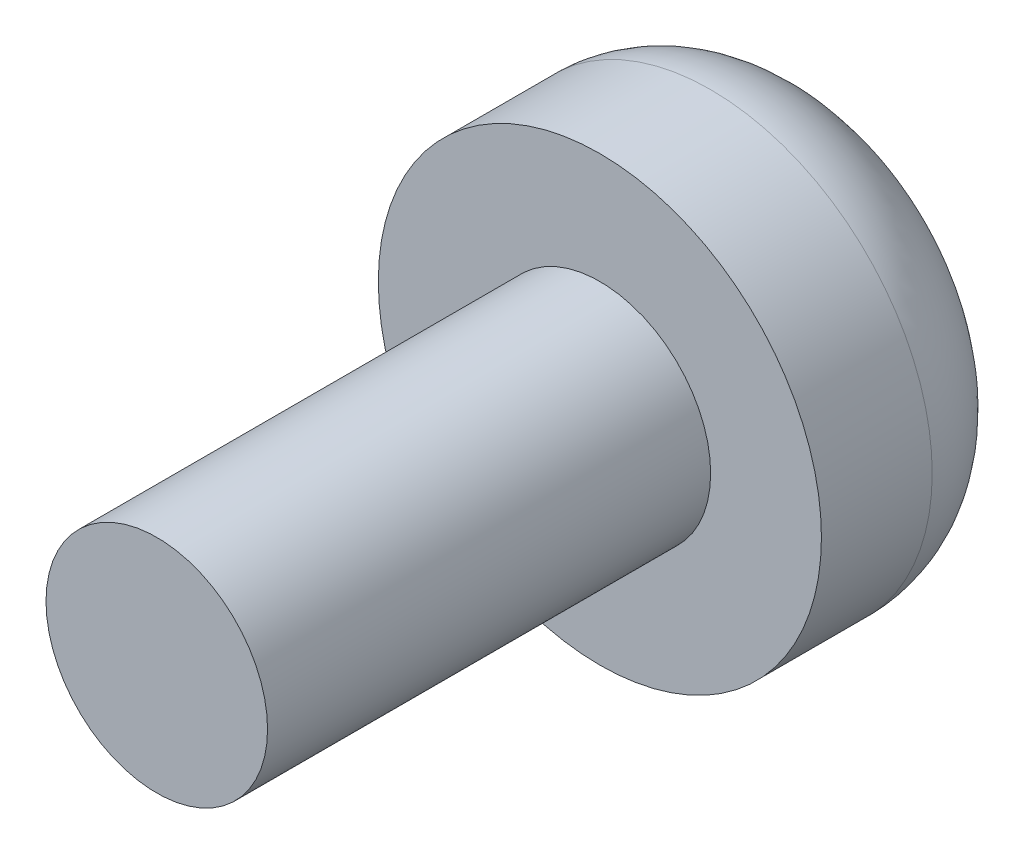
SolidWorks part; units mm, degrees
ref_plane "Front Plane" through (0, 0, 0) normal (0, 0, 1) x (1, 0, 0)
ref_plane "Top Plane" through (0, 0, 0) normal (0, 1, 0) x (1, 0, 0)
ref_plane "Right Plane" through (0, 0, 0) normal (1, 0, 0) x (0, 0, -1)
sketch "Sketch1" plane through (0, 0, 0) normal (0, 0, 1) x (1, 0, 0)
  circle A0 centre (0, 0) radius 1
  dimension "D1" = 2
extrude "Boss-Extrude1" add sketch "Sketch1" along normal blind 4
sketch "Sketch2" plane through (0, 0, 0) normal (0, 0, -1) x (-1, 0, 0)
  circle A0 centre (0, 0) radius 2
  dimension "D1" = 4
extrude "Boss-Extrude2" add sketch "Sketch2" along normal blind 2
fillet "Fillet1" radius 1 1 edges at (-2, 0, -2)
sketch "Sketch4" plane through (0, 0, -2) normal (0, 0, -1) x (-1, 0, 0)
  line L1 (0.9215, -0.0642) -> (0.5164, 0.766)
  line L2 (0.5164, 0.766) -> (-0.4052, 0.8302)
  line L3 (-0.4052, 0.8302) -> (-0.9215, 0.0642)
  line L4 (-0.9215, 0.0642) -> (-0.5164, -0.766)
  line L5 (-0.5164, -0.766) -> (0.4052, -0.8302)
  line L6 (0.4052, -0.8302) -> (0.9215, -0.0642)
  circle A0 centre (0, 0) radius 0.8 construction
  dimension "D1" = 0.8
extrude "Cut-Extrude2" cut sketch "Sketch4" against normal blind 1.5
fillet "Fillet2" radius 0.2 6 edges at (0.7189, -0.3509, -2) (-0.0556, 0.7981, -2) (0.6633, 0.4472, -2) (0.0556, -0.7981, -2) (-0.6633, -0.4472, -2) (-0.7189, 0.3509, -2)
